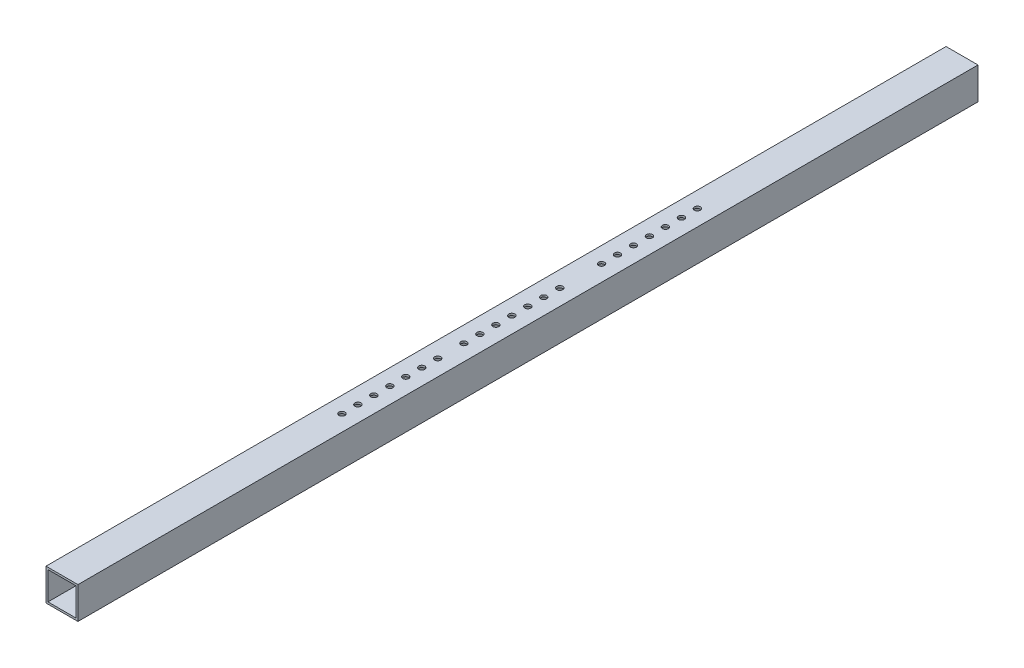
SolidWorks part; units mm, degrees
material "ALUMINUM 6061-T6"
ref_plane "Front Plane" through (0, 0, 0) normal (0, 0, 1) x (1, 0, 0)
ref_plane "Top Plane" through (0, 0, 0) normal (0, 1, 0) x (1, 0, 0)
ref_plane "Right Plane" through (0, 0, 0) normal (1, 0, 0) x (0, 0, -1)
sketch "Sketch1" plane through (0, 0, 0) normal (0, 0, 1) x (1, 0, 0)
  line L0 (11.1125, -11.1125) -> (11.1125, 11.1125)
  line L1 (-12.7, -12.7) -> (12.7, -12.7)
  line L2 (-12.7, -12.7) -> (-12.7, 12.7)
  line L3 (-12.7, 12.7) -> (12.7, 12.7)
  line L4 (12.7, -12.7) -> (12.7, 12.7)
  line L5 (-12.7, -12.7) -> (12.7, 12.7) construction
  line L6 (-12.7, 12.7) -> (12.7, -12.7) construction
  line L7 (-11.1125, 11.1125) -> (11.1125, 11.1125)
  line L8 (-11.1125, -11.1125) -> (-11.1125, 11.1125)
  line L9 (-11.1125, -11.1125) -> (11.1125, -11.1125)
  point P0 (0, 0)
  dimension "D1" = 25.4
  dimension "D2" = 25.4
  dimension "D3" = 1.5875
extrude "Boss-Extrude1" add sketch "Sketch1" along normal mid plane 715.518
sketch "Sketch2" plane through (0, -12.7, 0) normal (0, -1, 0) x (1, 0, 0)
  line L0 (-12.7, 357.759) -> (12.7, 357.759) construction
  circle A0 centre (0, -37.973) radius 2.3812
  circle A1 centre (0, -25.273) radius 2.3812
  circle A2 centre (0, -12.573) radius 2.3812
  circle A3 centre (0, 0.127) radius 2.3812
  circle A4 centre (0, 12.827) radius 2.3812
  circle A5 centre (0, 25.527) radius 2.3812
  circle A6 centre (0, 38.227) radius 2.3812
  dimension "D1" = 4.7625
  dimension "D2" = 12.7
  dimension "D3" = 12.7
  dimension "D4" = 12.7
  dimension "D5" = 12.7
  dimension "D6" = 12.7
  dimension "D7" = 12.7
  dimension "D8" = 357.632
extrude "Cut-Extrude1" cut sketch "Sketch2" against normal through all
sketch "Sketch3" plane through (0, -12.7, 0) normal (0, -1, 0) x (1, 0, 0)
  line L1 (-12.7, -357.759) -> (12.7, -357.759) construction
  circle A0 centre (0, 59.0186) radius 2.3812
  circle A1 centre (0, 71.7186) radius 2.3812
  circle A2 centre (0, 84.4186) radius 2.3812
  circle A3 centre (0, 109.8186) radius 2.3812
  circle A4 centre (0, 122.5186) radius 2.3812
  circle A5 centre (0, 135.2186) radius 2.3812
  circle A6 centre (0, 97.1186) radius 2.3812
  circle A7 centre (0, -71.1814) radius 2.3812
  circle A8 centre (0, -83.8814) radius 2.3812
  circle A9 centre (0, -96.5814) radius 2.3812
  circle A10 centre (0, -109.2814) radius 2.3812
  circle A11 centre (0, -121.9814) radius 2.3812
  circle A12 centre (0, -134.6814) radius 2.3812
  circle A13 centre (0, -147.3814) radius 2.3812
  dimension "D1" = 4.7625
  dimension "D9" = 4.7625
  dimension "D10" = 12.7
  dimension "D11" = 12.7
  dimension "D12" = 12.7
  dimension "D13" = 12.7
  dimension "D14" = 12.7
  dimension "D15" = 12.7
  dimension "D16" = 454.8776
  dimension "D8" = 248.4776
  dimension "D2" = 12.7
  dimension "D3" = 12.7
  dimension "D4" = 12.7
  dimension "D5" = 12.7
  dimension "D6" = 12.7
  dimension "D7" = 12.7
extrude "Cut-Extrude2" cut sketch "Sketch3" against normal through all
